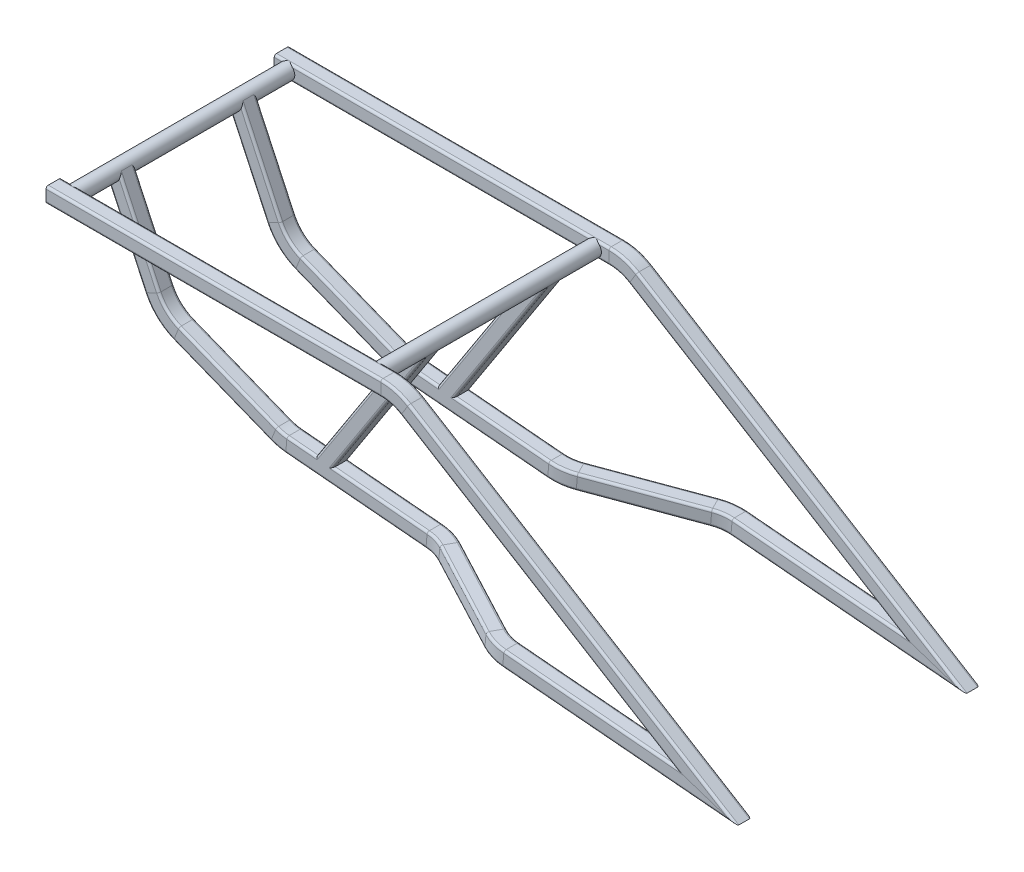
SolidWorks part; units mm, degrees
ref_plane "Front Plane" through (0, 0, 0) normal (0, 0, 1) x (1, 0, 0)
ref_plane "Top Plane" through (0, 0, 0) normal (0, 1, 0) x (1, 0, 0)
ref_plane "Right Plane" through (0, 0, 0) normal (1, 0, 0) x (0, 0, -1)
sketch "Sketch1" plane through (0, 0, 0) normal (0, 0, 1) x (1, 0, 0)
  line L0 (0, 0) -> (580.39, 0) construction
  line L1 (580.39, 0) -> (1100.1594, -318.5151) construction
  line L2 (533.4, 0) -> (368.1439, -254.4721) construction
  line L3 (1100.1594, -318.5151) -> (301.2499, -248.6196) construction
  line L4 (301.2499, -248.6196) -> (100.4886, -169.1986) construction
  line L5 (100.4886, -169.1986) -> (21.59, 0) construction
  dimension "D2" = 609.6
  dimension "D3" = 580.39
  dimension "D4" = 186.69
  dimension "D5" = 215.9
  dimension "D6" = 46.99
  dimension "D7" = 148.5
  dimension "D8" = 26.5
  dimension "D9" = 62
  dimension "D10" = 163.416
  dimension "D11" = 136.584
  dimension "D12" = 65
  dimension "D13" = 303.4231
  dimension "D14" = 21.59
ref_axis "Axis1" through (1100.1594, -318.5151, 0) along (0, 0, 1)
ref_plane "Plane1" through (-19.2978, -220.5753, 0) normal (-0.0872, -0.9962, 0) x (-0.9962, 0.0872, 0)
sketch3d "3DSketch1"
  line L0 (533.4, 0, 0) -> (368.1439, -254.4721, 0) construction
  line L1 (1100.1594, -318.5151, 0) -> (301.2499, -248.6196, 0) construction
  line L2 (0, 0, 0) -> (580.39, 0, 0) construction
  line L3 (580.39, 0, 0) -> (1100.1594, -318.5151, 0) construction
  line L4 (301.2499, -248.6196, 0) -> (100.4886, -169.1986, 0) construction
  line L5 (100.4886, -169.1986, 0) -> (21.59, 0, 0) construction
  line L6 (533.4, 0, 0) -> (368.1439, -254.4721, 0) construction
  line L7 (1100.1594, -318.5151, 0) -> (301.2499, -248.6196, 0) construction
  line L8 (0, 0, 0) -> (580.39, 0, 0) construction
  line L9 (580.39, 0, 0) -> (1100.1594, -318.5151, 0) construction
  line L10 (301.2499, -248.6196, 0) -> (100.4886, -169.1986, 0) construction
  line L11 (100.4886, -169.1986, 0) -> (21.59, 0, 0) construction
  line L12 (1100.1594, -318.5151, -190.5) -> (1100.1594, -318.5151, 190.5) construction
  line L13 (301.2499, -248.6196, -101.6) -> (301.2499, -248.6196, 101.6) construction
  line L14 (1100.1594, -318.5151, 190.5) -> (763.3991, -289.0524, 190.5)
  line L15 (730.1884, -286.1469, 182.8204) -> (579.6109, -272.973, 109.2796)
  line L16 (546.4003, -270.0675, 101.6) -> (312.313, -249.5875, 101.6)
  line L17 (1100.1594, -318.5151, 190.5) -> (598.7138, -11.2288, 190.5)
  line L18 (558.8994, 0, 190.5) -> (0, 0, 190.5)
  line L19 (368.1439, -254.4721, 101.6) -> (533.4, 0, 101.6)
  line L20 (533.4, 0, 190.5) -> (533.4, 0, 0)
  line L21 (21.59, 0, 0) -> (21.59, 0, 190.5)
  line L22 (290.9233, -244.5344, 101.6) -> (128.6977, -180.3581, 101.6)
  line L23 (87.668, -141.7047, 101.6) -> (21.59, 0, 101.6)
  arc A0 (128.6977, -180.3581, 101.6) -> (87.668, -141.7047, 101.6) centre (156.7286, -109.5011, 101.6) ccw
  arc A1 (312.313, -249.5875, 101.6) -> (290.9233, -244.5344, 101.6) centre (318.9543, -173.6775, 101.6) ccw
  arc A2 (579.6109, -272.973, 109.2796) -> (546.4003, -270.0675, 101.6) centre (546.4003, -270.0675, 177.8) ccw
  arc A3 (763.3991, -289.0524, 190.5) -> (730.1884, -286.1469, 182.8204) centre (763.3991, -289.0524, 114.3) ccw
  arc A4 (598.7138, -11.2288, 190.5) -> (558.8994, 0, 190.5) centre (558.8994, -76.2, 190.5) ccw
  point P8 (1100.1594, -318.5151, 0)
  point P14 (301.2499, -248.6196, 0)
  point P26 (100.4886, -169.1986, 101.6)
  point P27 (156.7286, -109.5011, 25.4)
  point P30 (301.2499, -248.6196, 101.6)
  point P32 (318.9543, -173.6775, 25.4)
  point P35 (563.8867, -271.5973, 101.6)
  point P36 (553.0415, -194.1574, 177.8)
  point P39 (745.9126, -287.5225, 190.5)
  point P40 (756.7578, -364.9624, 114.3)
  point P43 (580.39, 0, 190.5)
  point P44 (558.8994, -76.2, 266.7)
  dimension "D5" = 76.2
  dimension "D1" = 381
  dimension "D2" = 203.2
  dimension "D3" = 355.6
  dimension "D4" = 203.2
sketch3d "3DSketch2"
  line L5 (0, 8.89, 177.8) -> (0, -8.89, 177.8)
  line L6 (0, 12.7, 181.61) -> (0, 12.7, 199.39)
  line L7 (0, 8.89, 203.2) -> (0, -8.89, 203.2)
  line L8 (0, -12.7, 181.61) -> (0, -12.7, 199.39)
  line L9 (0, 12.7, 177.8) -> (0, -12.7, 203.2) construction
  line L10 (0, 12.7, 203.2) -> (0, -12.7, 177.8) construction
  arc A0 (0, -8.89, 177.8) -> (0, -12.7, 181.61) centre (0, -8.89, 181.61) ccw
  arc A1 (0, -8.89, 203.2) -> (0, -12.7, 199.39) centre (0, -8.89, 199.39) ccw
  arc A2 (0, 12.7, 199.39) -> (0, 8.89, 203.2) centre (0, 8.89, 199.39) ccw
  arc A3 (0, 8.89, 177.8) -> (0, 12.7, 181.61) centre (0, 8.89, 181.61) ccw
  point P0 (0, 0, 190.5)
  point P9 (0, -12.7, 177.8)
  point P11 (-3.81, -8.89, 181.61)
  point P14 (0, -12.7, 203.2)
  point P16 (3.81, -8.89, 199.39)
  point P19 (0, 12.7, 203.2)
  point P21 (3.81, 8.89, 199.39)
  point P24 (0, 12.7, 177.8)
  point P26 (3.81, 8.89, 181.61)
  dimension "D1" = 25.4
  dimension "D2" = 3.81
sweep "Sweep1" add profiles "3DSketch2" path "3DSketch1"
sketch3d "3DSketch3"
  line L0 (544.0511, -6.9169, 92.71) -> (544.0511, -6.9169, 110.49)
  line L5 (522.7489, 6.9169, 88.9) -> (544.0511, -6.9169, 114.3) construction
  line L6 (540.8558, -4.8418, 114.3) -> (525.9442, 4.8418, 114.3)
  line L7 (368.1439, -254.4721, 101.6) -> (533.4, 0, 101.6) construction
  line L8 (544.0511, -6.9169, 88.9) -> (522.7489, 6.9169, 114.3) construction
  line L9 (522.7489, 6.9169, 110.49) -> (522.7489, 6.9169, 92.71)
  line L10 (525.9442, 4.8418, 88.9) -> (540.8558, -4.8418, 88.9)
  arc A0 (522.7489, 6.9169, 92.71) -> (525.9442, 4.8418, 88.9) centre (525.9442, 4.8418, 92.71) ccw
  arc A1 (544.0511, -6.9169, 110.49) -> (540.8558, -4.8418, 114.3) centre (540.8558, -4.8418, 110.49) ccw
  arc A2 (525.9442, 4.8418, 114.3) -> (522.7489, 6.9169, 110.49) centre (525.9442, 4.8418, 110.49) ccw
  arc A3 (544.0511, -6.9169, 92.71) -> (540.8558, -4.8418, 88.9) centre (540.8558, -4.8418, 92.71) ccw
  point P5 (533.4, 0, 101.6)
  point P9 (533.4, 0, 101.6)
  point P12 (0, 0, 0)
  point P14 (546.4128, -8.4506, 86.0841)
  point P16 (533.4, 0, 101.6)
  point P17 (522.7489, 6.9169, 88.9)
  point P18 (523.8691, 1.6465, 92.71)
  point P21 (544.0511, -6.9169, 114.3)
  point P22 (538.7807, -8.0372, 110.49)
  point P25 (522.7489, 6.9169, 114.3)
  point P26 (523.8691, 1.6465, 110.49)
  point P29 (544.0511, -6.9169, 88.9)
  point P31 (542.9309, -1.6465, 92.71)
  dimension "D1" = 25.4
  dimension "D2" = 3.81
sweep "Sweep2" add profiles "3DSketch3" path "3DSketch1<5>"
sketch3d "3DSketch1<5>" same geometry as "3DSketch1"
sweep "Sweep3" add path "3DSketch1<6>" circular profile diameter 25.4 parameters "D3"=25.4
sketch3d "3DSketch1<6>" same geometry as "3DSketch1"
sweep "Sweep4" add path "3DSketch1<7>" circular profile diameter 25.4 parameters "D3"=25.4
sketch3d "3DSketch1<7>" same geometry as "3DSketch1"
mirror "Mirror3" about plane through (0, 0, 0) normal (0, 0, 1) of bodies 104
equation "\"width_high\"= 16 - 1in"
equation "\"width_low\"= 9 - 1in"
equation "\"bar_width\"= 1in"
equation "\"bar_fillet\"= 0.15in"
equation "\"D1@3DSketch2\"=\"bar_width\""
equation "\"frame_fillet\"= 3in"
equation "\"D5@3DSketch1\"=\"frame_fillet\""
equation "\"D2@3DSketch3\"=\"bar_fillet\""
equation "\"D3@Sweep3\"=\"bar_width\""
equation "\"D3@Sweep4\"=\"bar_width\""
